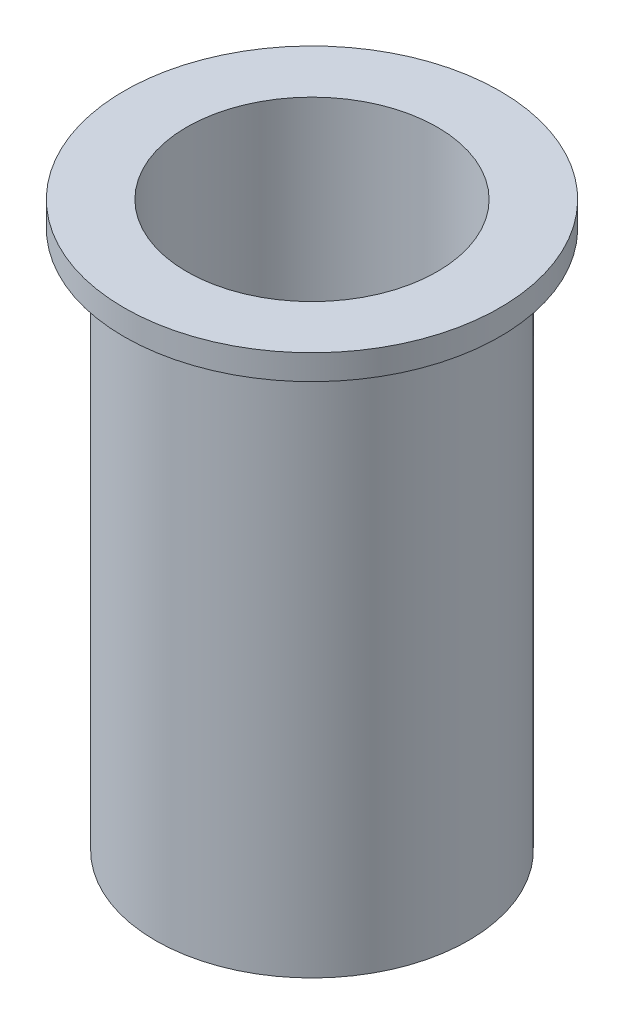
SolidWorks part; units mm, degrees
ref_plane "Front Plane" through (0, 0, 0) normal (0, 0, 1) x (1, 0, 0)
ref_plane "Top Plane" through (0, 0, 0) normal (0, 1, 0) x (1, 0, 0)
ref_plane "Right Plane" through (0, 0, 0) normal (1, 0, 0) x (0, 0, -1)
sketch "Sketch1" plane through (0, 0, 0) normal (0, 1, 0) x (1, 0, 0)
  circle A0 centre (0, 0) radius 2.5 construction
  circle A1 centre (0, 0) radius 3
  dimension "D1" = 6
  dimension "D2" = 5
extrude "Boss-Extrude1" add sketch "Sketch1" against normal blind 0.4
sketch "Sketch2" plane through (0, -0.4, 0) normal (0, -1, 0) x (1, 0, 0)
  circle A0 centre (0, 0) radius 2.5 construction
  circle A1 centre (0, 0) radius 2.5
extrude "Boss-Extrude2" add sketch "Sketch2" along normal blind 8.6
shell "Shell1" thickness 0.5 removed face at (0, 0, 3)
sketch "Sketch3" plane through (0, -9, 0) normal (0, -1, 0) x (1, 0, 0)
  circle A0 centre (0, 0) radius 1.5
  dimension "D1" = 3
extrude "Cut-Extrude1" cut sketch "Sketch3" against normal up to next
